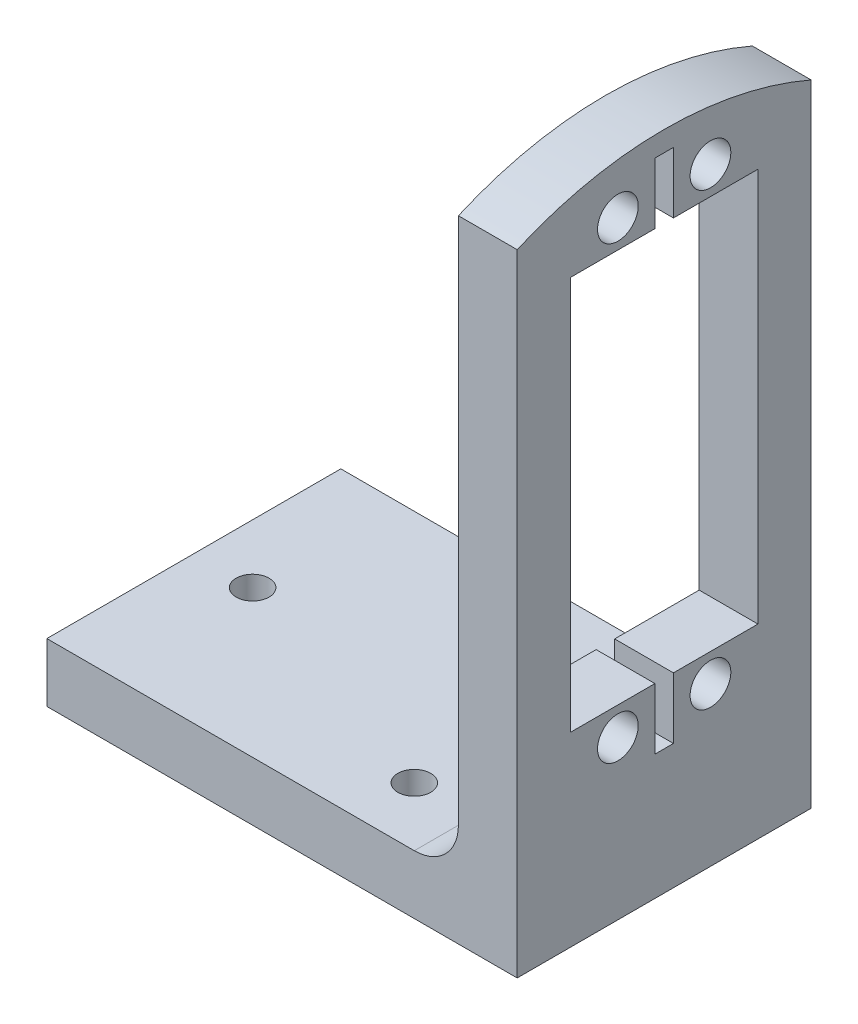
SolidWorks part; units mm, degrees
ref_plane "Front Plane" through (0, 0, 0) normal (0, 0, 1) x (1, 0, 0)
ref_plane "Top Plane" through (0, 0, 0) normal (0, 1, 0) x (1, 0, 0)
ref_plane "Right Plane" through (0, 0, 0) normal (1, 0, 0) x (0, 0, -1)
sketch "Sketch3" plane through (0, 0, 0) normal (1, 0, 0) x (0, 0, -1)
  line L0 (5.748, 56.3) -> (26.002, 13.755) construction
  line L1 (0, 0) -> (31.75, 0)
  line L2 (0, 0) -> (0, 69)
  line L3 (0, 69) -> (31.75, 69)
  line L4 (31.75, 0) -> (31.75, 69)
  line L5 (5.748, 56.3) -> (14.875, 56.3)
  line L6 (5.748, 56.3) -> (5.748, 13.755)
  line L7 (5.748, 13.755) -> (14.875, 13.755)
  line L8 (26.002, 56.3) -> (26.002, 13.755)
  line L9 (26.002, 56.3) -> (5.748, 13.755) construction
  line L10 (10.875, 59.3275) -> (20.875, 10.7275) construction
  line L11 (10.875, 10.7275) -> (20.875, 59.3275) construction
  line L12 (16.875, 13.755) -> (26.002, 13.755)
  line L13 (14.875, 13.755) -> (14.875, 7.151)
  line L14 (14.875, 7.151) -> (16.875, 7.151)
  line L15 (16.875, 13.755) -> (16.875, 7.151)
  line L16 (15.875, 35.0275) -> (-939.9401, 35.0275) construction
  line L17 (14.875, 62.904) -> (16.875, 62.904)
  line L18 (14.875, 56.3) -> (14.875, 62.904)
  line L19 (16.875, 56.3) -> (16.875, 62.904)
  line L20 (16.875, 56.3) -> (26.002, 56.3)
  circle A0 centre (10.875, 10.7275) radius 2.2
  circle A1 centre (20.875, 10.7275) radius 2.2
  circle A2 centre (10.875, 59.3275) radius 2.2
  circle A3 centre (20.875, 59.3275) radius 2.2
  point P13 (15.875, 7.151)
  point P22 (15.875, 35.0275)
  point P23 (15.875, 35.0275)
  point P32 (15.875, 25.4)
  point P33 (15.875, 44.45)
  point P34 (15.875, 0)
  point P35 (15.875, 44.45)
  dimension "D3" = 4.4
  dimension "D1" = 10
  dimension "D2" = 48.6
  dimension "D4" = 42.545
  dimension "D5" = 20.254
  dimension "D6" = 2
  dimension "D7" = 6.604
  dimension "D8" = 30.9
  dimension "D9" = 25.4
  dimension "D10" = 31.75
  dimension "D12" = 12.7
extrude "Boss-Extrude1" add sketch "Sketch3" along normal blind 6.35
sketch "Sketch5" plane through (6.35, 0, 0) normal (1, 0, 0) x (0, 0, -1)
  line L1 (0, 0) -> (31.75, 0)
  line L2 (0, 0) -> (0, -6.35)
  line L3 (0, -6.35) -> (31.75, -6.35)
  line L4 (31.75, 0) -> (31.75, -6.35)
  dimension "D1" = 6.35
extrude "Boss-Extrude2" add sketch "Sketch5" against normal blind 50.8
fillet "Fillet1" radius 4.7625 1 edges at (0, 0, -15.875)
sketch "Sketch6" plane through (0, 0, 0) normal (0, 1, 0) x (1, 0, 0)
  line L0 (-44.45, 0) -> (-4.7625, 0) construction
  line L1 (-4.7625, 0) -> (-4.7625, 31.75) construction
  line L2 (-44.45, 31.75) -> (-44.45, 0) construction
  line L3 (0, 15.875) -> (-33.0413, 15.875) construction
  line L4 (0, 31.75) -> (0, 0) construction
  circle A0 centre (-11.1125, 6.35) radius 1.777
  circle A2 centre (-38.1, 15.875) radius 1.777
  circle A3 centre (-11.1125, 25.4) radius 1.777
  dimension "D1" = 3.554
  dimension "D2" = 6.35
  dimension "D3" = 6.35
  dimension "D4" = 6.35
extrude "Cut-Extrude1" cut sketch "Sketch6" against normal through all
sketch "Sketch7" plane through (6.35, 0, 0) normal (1, 0, 0) x (0, 0, -1)
  line L0 (31.75, 69) -> (0, 69) construction
  line L1 (0, -6.35) -> (31.75, -6.35) construction
  line L2 (0, 61.7742) -> (0, 69)
  line L3 (0, 69) -> (0, -6.35) construction
  line L4 (0, 69) -> (31.75, 69)
  line L5 (31.75, 69) -> (31.75, 61.7742)
  line L6 (31.75, -6.35) -> (31.75, 69) construction
  arc A0 (31.75, 61.7742) -> (0, 61.7742) centre (15.875, 25.4) ccw
  point P6 (15.875, 69)
  dimension "D2" = 79.375
  dimension "D1" = 31.75
extrude "Cut-Extrude2" cut sketch "Sketch7" against normal through all
equation "\"D1@Sketch6\" = 3.3mm + \"normTol\""
equation "\"tightTol\"= 0.005in"
equation "\"normTol\"= 0.01in"
equation "\"looseTol\"= 0.02in"
